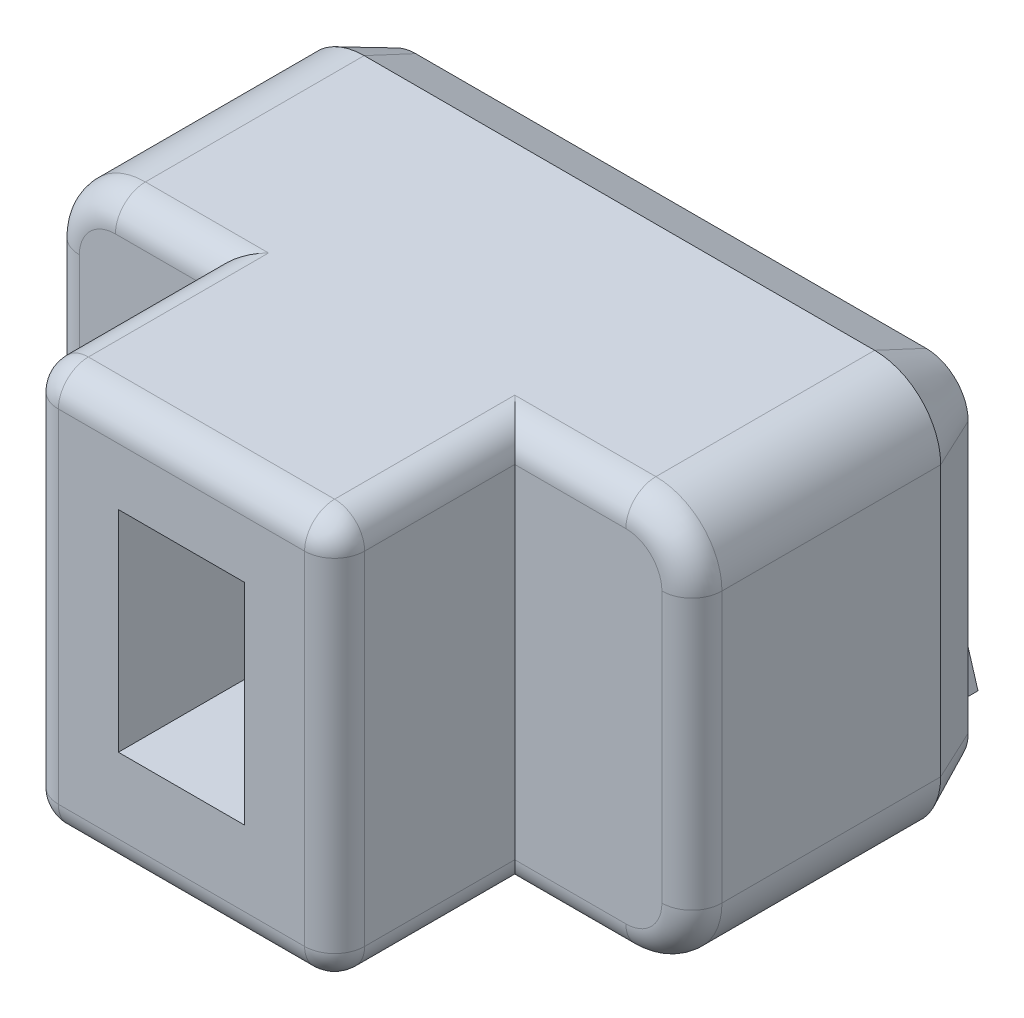
SolidWorks part; units mm, degrees
ref_plane "Plan de face" through (0, 0, 0) normal (0, 0, 1) x (1, 0, 0)
ref_plane "Plan de dessus" through (0, 0, 0) normal (0, 1, 0) x (1, 0, 0)
ref_plane "Plan de droite" through (0, 0, 0) normal (1, 0, 0) x (0, 0, -1)
sketch "Esquisse2" plane through (0, 0, 0) normal (0, 0, 1) x (1, 0, 0)
  line L1 (1.1, 0) -> (9.6, 0)
  line L2 (0, 1.1) -> (0, 5.6)
  line L3 (1.1, 6.7) -> (9.6, 6.7)
  line L4 (10.7, 1.1) -> (10.7, 5.6)
  arc A0 (9.6, 6.7) -> (10.7, 5.6) centre (9.6, 5.6) cw
  arc A1 (9.6, 0) -> (10.7, 1.1) centre (9.6, 1.1) ccw
  arc A2 (1.1, 0) -> (0, 1.1) centre (1.1, 1.1) cw
  arc A3 (0, 5.6) -> (1.1, 6.7) centre (1.1, 5.6) cw
  point P7 (10.7, 6.7)
  point P12 (0, 0)
  point P15 (0, 6.7)
  dimension "D3" = 1.1
  dimension "D1" = 10.7
  dimension "D2" = 6.7
extrude "Boss.-Extru.1" add sketch "Esquisse2" along normal blind 8
sketch "Esquisse3" plane through (0, 0, 8) normal (0, 0, 1) x (1, 0, 0)
  line L0 (0, 5.6) -> (0, 1.1) construction
  line L1 (4.15, 5.25) -> (6.25, 5.25)
  line L2 (4.15, 5.25) -> (4.15, 1.75)
  line L3 (4.15, 1.75) -> (6.25, 1.75)
  line L4 (6.25, 5.25) -> (6.25, 1.75)
  line L5 (10.7, 1.1) -> (10.7, 5.6) construction
  line L6 (9.6, 6.7) -> (1.1, 6.7) construction
  line L7 (1.1, 0) -> (9.6, 0) construction
  dimension "D1" = 2.1
  dimension "D2" = 3.5
  dimension "D3" = 4.15
  dimension "D4" = 4.45
  dimension "D5" = 1.45
  dimension "D6" = 1.75
extrude "Enlèv. mat.-Extru.1" cut sketch "Esquisse3" against normal blind 3
sketch "Esquisse4" plane through (0, 0, 8) normal (0, 0, 1) x (1, 0, 0)
  line L0 (2.65, 6.7) -> (2.65, 0)
  line L1 (9.6, 6.7) -> (1.1, 6.7) construction
  line L2 (1.1, 0) -> (9.6, 0) construction
  line L3 (2.65, 0) -> (7.75, 0)
  line L4 (7.75, 0) -> (7.75, 6.7)
  line L5 (7.75, 6.7) -> (2.65, 6.7)
  line L6 (4.15, 5.25) -> (4.15, 1.75) construction
  line L7 (6.25, 1.75) -> (6.25, 5.25) construction
  dimension "D1" = 1.5
  dimension "D2" = 1.5
extrude "Enlèv. mat.-Extru.2" cut sketch "Esquisse4" against normal blind 3 flip side to cut
fillet "Congé1" radius 0.5 18 edges at (8.675, 0, 5) (10.3778, 0.3222, 5) (10.7, 3.35, 5) (10.3778, 6.3778, 5) (1.875, 6.7, 5) (0.3222, 6.3778, 5) (1.875, 0, 5) (0.3222, 0.3222, 5) (7.75, 6.7, 6.5) (2.65, 6.7, 6.5) (7.75, 0, 6.5) (2.65, 0, 6.5) (2.65, 3.35, 8) (5.2, 6.7, 8) (7.75, 3.35, 8) (5.2, 0, 8) (8.675, 6.7, 5) (0, 3.35, 5)
chamfer "Chanfrein1" distance 0.4 angle 65 8 edges at (5.35, 0, 0) (10.3778, 0.3222, 0) (0.3222, 0.3222, 0) (10.7, 3.35, 0) (0, 3.35, 0) (10.3778, 6.3778, 0) (0.3222, 6.3778, 0) (5.35, 6.7, 0) first distance on face at (5.35, 3.35, 0)
sketch "Esquisse5" plane through (0, 0, 0) normal (0, 0, 1) x (1, 0, 0)
  line L0 (-0.9378, 5.093) -> (11.6517, 5.093) construction
  text T0 "VNAV" font "Corbel" height 3.5
extrude "Enlèv. mat.-Extru.3" cut sketch "Esquisse5" along normal blind 0.2
extrude "Boss.-Extru.2" add sketch "Esquisse5<4>" against normal blind 0.2
sketch "Esquisse5<4>" plane through (0, 0, 0) normal (0, 0, 1) x (1, 0, 0) same geometry as "Esquisse5"
